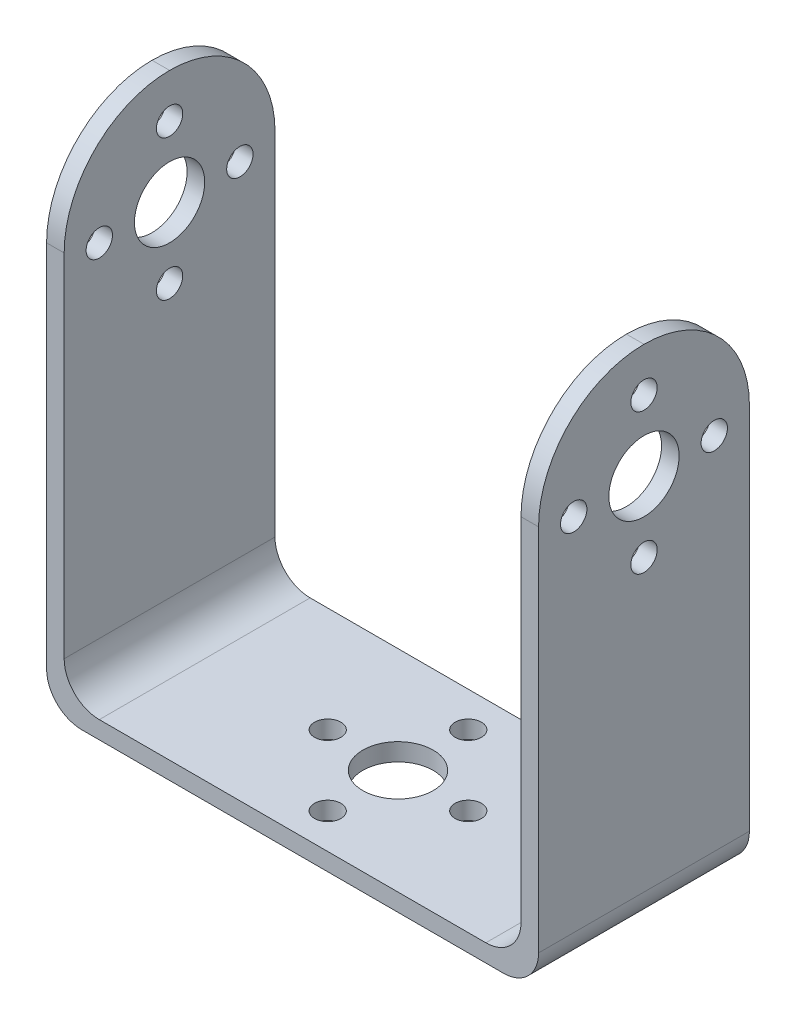
SolidWorks part; units mm, degrees
ref_plane "Front Plane" through (0, 0, 0) normal (0, 0, 1) x (1, 0, 0)
ref_plane "Top Plane" through (0, 0, 0) normal (0, 1, 0) x (1, 0, 0)
ref_plane "Right Plane" through (0, 0, 0) normal (1, 0, 0) x (0, 0, -1)
sketch "Sketch1" plane through (0, 0, 0) normal (0, 0, 1) x (1, 0, 0)
  line L0 (-78.3013, 50.4267) -> (-78.3013, -5.5733)
  line L1 (-78.3013, -5.5733) -> (-26.3013, -5.5733)
  line L2 (-26.3013, -5.5733) -> (-26.3013, 50.4267)
  line L3 (-80.3013, 50.4267) -> (-80.3013, -7.5733)
  line L4 (-80.3013, -7.5733) -> (-24.3013, -7.5733)
  line L5 (-24.3013, -7.5733) -> (-24.3013, 50.4267)
  line L6 (-80.3013, 50.4267) -> (-78.3013, 50.4267)
  line L7 (-26.3013, 50.4267) -> (-24.3013, 50.4267)
  dimension "D1" = 2
extrude "Boss-Extrude1" add sketch "Sketch1" along normal blind 24
sketch "Sketch2" plane through (-24.3013, 0, 0) normal (1, 0, 0) x (0, 0, -1)
  line L0 (-24, -7.5733) -> (0, -7.5733) construction
  line L1 (-24, -7.5733) -> (-24, 50.4267) construction
  circle A0 centre (-12, 37.4267) radius 4
  circle A1 centre (-4, 37.4267) radius 1.5
  circle A2 centre (-12, 29.4267) radius 1.5
  circle A3 centre (-20, 37.4267) radius 1.5
  circle A4 centre (-12, 45.4267) radius 1.5
  point P2 (-12, -7.5733)
  point P18 (-12, 37.4267)
  dimension "D1" = 45
  dimension "D3" = 8
  dimension "D2" = 12
  dimension "D4" = 45
  dimension "D5" = 4
extrude "Cut-Extrude1" cut sketch "Sketch2" against normal blind 19
sketch "Sketch3" plane through (-80.3013, 0, 0) normal (-1, 0, 0) x (0, 0, 1)
  line L0 (24, -7.5733) -> (0, -7.5733) construction
  line L1 (0, 50.4267) -> (0, -7.5733) construction
  circle A0 centre (12, 37.4267) radius 4
  circle A1 centre (20, 37.4267) radius 1.5
  circle A2 centre (12, 29.4267) radius 1.5
  circle A3 centre (12, 37.4267) radius 4
  circle A4 centre (4, 37.4267) radius 1.5
  circle A5 centre (12, 37.4267) radius 4
  circle A6 centre (12, 45.4267) radius 1.5
  circle A7 centre (12, 37.4267) radius 4
  point P20 (12, 37.4267)
  dimension "D1" = 45
  dimension "D3" = 8
  dimension "D4" = 45
  dimension "D2" = 12
  dimension "D5" = 4
extrude "Cut-Extrude2" cut sketch "Sketch3" against normal blind 2 contours A4 | A6 | A1 | A2 | A0
fillet "Fillet1" radius 12 4 edges at (-25.3013, 50.4267, 0) (-79.3013, 50.4267, 0) (-79.3013, 50.4267, 24) (-25.3013, 50.4267, 24)
sketch "Sketch4" plane through (0, -7.5733, 0) normal (0, -1, 0) x (1, 0, 0)
  line L0 (-80.3013, 24) -> (-24.3013, 24) construction
  line L1 (-24.3013, 24) -> (-24.3013, 0) construction
  circle A0 centre (-52.3013, 12) radius 4
  circle A1 centre (-60.3013, 12) radius 1.5
  circle A2 centre (-52.3013, 20) radius 1.5
  circle A3 centre (-52.3013, 12) radius 4
  circle A4 centre (-44.3013, 12) radius 1.5
  circle A5 centre (-52.3013, 12) radius 4
  circle A6 centre (-52.3013, 4) radius 1.5
  circle A7 centre (-52.3013, 12) radius 4
  point P20 (-52.3013, 12)
  dimension "D1" = 12
  dimension "D3" = 8
  dimension "D2" = 28
  dimension "D4" = 4
extrude "Cut-Extrude4" cut sketch "Sketch4" against normal blind 2 contours A4 | A6 | A1 | A0 | A2 | A4 | A6 region at (-44.3013, -7.5733, 12) region at (-52.3013, -7.5733, 4)
fillet "Fillet2" radius 4 4 edges at (-24.3013, -7.5733, 12) (-80.3013, -7.5733, 12) (-26.3013, -5.5733, 12) (-78.3013, -5.5733, 12)
